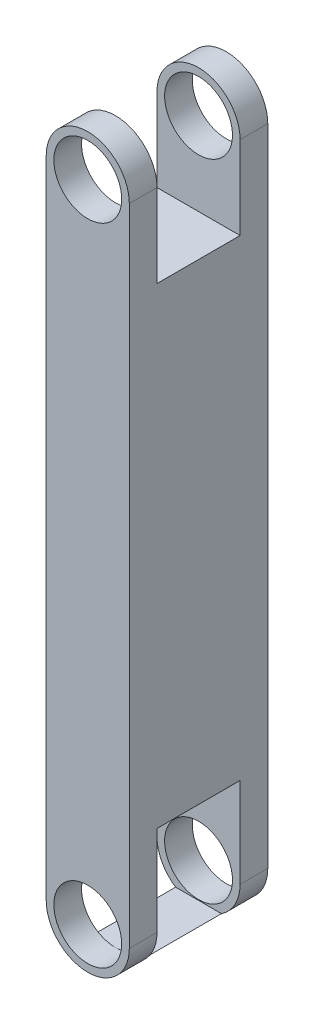
SolidWorks part; units mm, degrees
ref_plane "Piano frontale" through (0, 0, 0) normal (0, 0, 1) x (1, 0, 0)
ref_plane "Piano superiore" through (0, 0, 0) normal (0, 1, 0) x (1, 0, 0)
ref_plane "Piano destro" through (0, 0, 0) normal (1, 0, 0) x (0, 0, -1)
sketch "Schizzo1" plane through (0, 0, 0) normal (0, 0, 1) x (1, 0, 0)
  line L0 (0, -24.6565) -> (0, 24.6565) construction
  line L1 (0, 46.58) -> (0, 0) construction
  line L2 (3.575, 0) -> (-3.575, 0) construction
  line L4 (-3, 0) -> (-3, 46.58)
  line L5 (-2.5, 49.03) -> (3.5, 49.03) construction
  line L6 (3, 0) -> (3, 46.58)
  line L9 (-1000, 23.29) -> (49000, 23.29) construction
  circle A0 centre (0, 0) radius 2.45
  circle A1 centre (0, 46.58) radius 2.45
  arc A2 (-3, 46.58) -> (3, 46.58) centre (0, 46.58) cw
  arc A3 (-3, 0) -> (3, 0) centre (0, 0) ccw
  point P7 (0, 23.29)
  dimension "D1" = 4.9
  dimension "D2" = 4.9
  dimension "D7" = 3
  dimension "D5" = 3
  dimension "D3" = 46.58
  dimension "D4" = 23.29
extrude "Estrusione-Estrusione1" add sketch "Schizzo1" along normal blind 5 and the other way blind 5
sketch "Schizzo2" plane through (0, 0, 0) normal (1, 0, 0) x (0, 0, -1)
  line L0 (-3, 49.58) -> (3, 49.58)
  line L1 (-3, 49.58) -> (-3, 40.58)
  line L2 (3, 49.58) -> (3, 40.58)
  line L3 (-3, 40.58) -> (3, 40.58)
  line L4 (5, 49.58) -> (-5, 49.58) construction
  line L5 (0, 3.575) -> (0, -3.575) construction
  line L6 (3, -2.5) -> (3, 6.5)
  line L7 (3, -2.5) -> (-3, -2.5)
  line L8 (-3, -2.5) -> (-3, 6.5)
  line L9 (3, 6.5) -> (-3, 6.5)
  line L10 (5, 0) -> (5, 46.58) construction
  line L11 (5, -3) -> (5, 0) construction
  line L12 (-5, 0) -> (-5, -3) construction
  line L13 (-5, 0) -> (-5, 46.58) construction
  point P15 (0, 23.54)
  dimension "D1" = 6
  dimension "D2" = 3
  dimension "D3" = 9
  dimension "D5" = 6.5
  dimension "D6" = 2
  dimension "D7" = 2
  dimension "D8" = 2
  dimension "D9" = 2
  dimension "D4" = 2
extrude "Taglio-Estrusione1" cut sketch "Schizzo2" against normal through all and the other way through all
